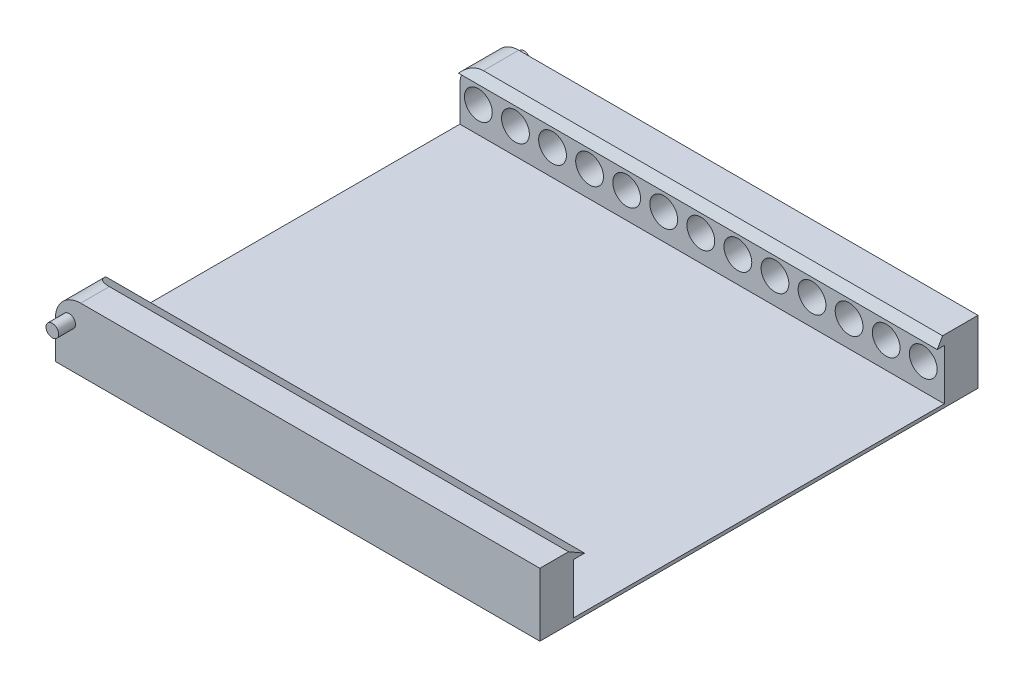
SolidWorks part; units mm, degrees
material "3003 Alloy"
ref_plane "Front Plane" through (0, 0, 0) normal (0, 0, 1) x (1, 0, 0)
ref_plane "Top Plane" through (0, 0, 0) normal (0, 1, 0) x (1, 0, 0)
ref_plane "Right Plane" through (0, 0, 0) normal (1, 0, 0) x (0, 0, -1)
sketch "Sketch2" plane through (0, 0, 0) normal (1, 0, 0) x (0, 0, -1)
  line L0 (-260, 0) -> (260, 0)
  line L1 (-260, 0) -> (-260, 75)
  line L2 (260, 0) -> (260, 75)
  line L3 (-260, 75) -> (-207, 75)
  line L4 (-220, 4) -> (220, 4)
  line L5 (0, 0) -> (0, 8) construction
  line L6 (-220, 4) -> (-220, 64)
  line L7 (220, 4) -> (220, 64)
  line L8 (-220, 64) -> (-207, 64)
  line L9 (-207, 64) -> (-207, 75)
  line L10 (220, 64) -> (207, 64)
  line L11 (207, 64) -> (207, 75)
  line L12 (207, 75) -> (260, 75)
  point P10 (0, 4)
  dimension "D1" = 520
  dimension "D2" = 75
  dimension "D3" = 13
  dimension "D4" = 440
  dimension "D5" = 4
  dimension "D6" = 60
  dimension "D7" = 13
extrude "Boss-Extrude1" add sketch "Sketch2" against normal blind 575
chamfer "Chamfer1" distance 19 angle 30 2 edges at (-287.5, 75, -207) (-287.5, 75, 207) first distance on face at (-287.5, 69.5, -207) first distance on face at (-287.5, 75, 233.5)
fillet "Fillet1" radius 30 2 edges at (-575, 75, 243) (-575, 75, -238.9848)
sketch "Sketch3" plane through (0, 0, 0) normal (0, 0, 1) x (1, 0, 0)
  line L0 (0, 75) -> (0, 0) construction
  line L1 (-575, 0) -> (0, 0) construction
  circle A0 centre (-25, 35) radius 16.5
  circle A1 centre (-69, 35) radius 16.5
  circle A2 centre (-113, 35) radius 16.5
  circle A3 centre (-157, 35) radius 16.5
  circle A4 centre (-201, 35) radius 16.5
  circle A5 centre (-245, 35) radius 16.5
  circle A6 centre (-289, 35) radius 16.5
  circle A7 centre (-333, 35) radius 16.5
  circle A8 centre (-377, 35) radius 16.5
  circle A9 centre (-421, 35) radius 16.5
  circle A10 centre (-465, 35) radius 16.5
  circle A11 centre (-509, 35) radius 16.5
  circle A12 centre (-553, 35) radius 16.5
  dimension "D1" = 33
  dimension "D2" = 25
  dimension "D3" = 35
  dimension "D4" = 13
extrude "Cut-Extrude1" cut sketch "Sketch3" against normal blind 250 and the other way blind 250
sketch "Sketch4" plane through (0, 0, 260) normal (0, 0, 1) x (1, 0, 0)
  line L0 (-575, 45) -> (-575, 0) construction
  line L1 (-545, 75) -> (0, 75) construction
  circle A0 centre (-558.68, 50) radius 7.5
  dimension "D2" = 15
  dimension "D1" = 16.32
  dimension "D3" = 25
extrude "Boss-Extrude2" add sketch "Sketch4" along normal blind 20
sketch "Sketch5" plane through (0, 0, -260) normal (0, 0, -1) x (-1, 0, 0)
  line L0 (575, 0) -> (575, 45) construction
  line L1 (545, 75) -> (0, 75) construction
  circle A0 centre (558.68, 50) radius 7.5
  dimension "D1" = 15
  dimension "D2" = 16.32
  dimension "D3" = 25
extrude "Boss-Extrude3" add sketch "Sketch5" along normal blind 20
